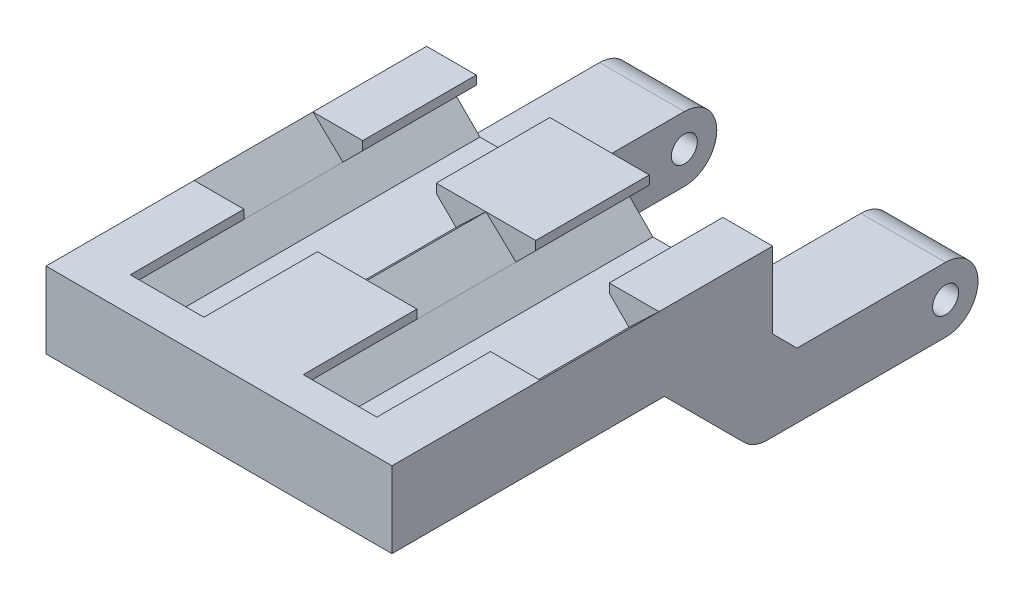
SolidWorks part; units mm, degrees
ref_plane "Front Plane" through (0, 0, 0) normal (0, 0, 1) x (1, 0, 0)
ref_plane "Top Plane" through (0, 0, 0) normal (0, 1, 0) x (1, 0, 0)
ref_plane "Right Plane" through (0, 0, 0) normal (1, 0, 0) x (0, 0, -1)
sketch "Sketch1" plane through (0, 0, 0) normal (0, 0, 1) x (1, 0, 0)
  line L154 (-20, -0.2) -> (-20, -9)
  line L155 (-20, -9) -> (20, -9)
  line L156 (20, -9) -> (20, -0.2)
  line L157 (-6.25, -6) -> (-13.75, -6) construction
  line L171 (14.2535, -0.2) -> (20, -0.2)
  line L172 (14.2535, -1.2207) -> (14.2535, -0.2)
  line L173 (16.5328, -3.5) -> (14.2535, -1.2207)
  line L174 (13.8328, -6.2) -> (16.5328, -3.5)
  line L175 (6.1672, -6.2) -> (13.8328, -6.2)
  line L176 (3.4672, -3.5) -> (6.1672, -6.2)
  line L177 (5.7465, -1.2207) -> (3.4672, -3.5)
  line L178 (5.7465, -0.2) -> (5.7465, -1.2207)
  line L179 (-5.7465, -0.2) -> (5.7465, -0.2)
  line L180 (-5.7465, -1.2207) -> (-5.7465, -0.2)
  line L181 (-3.4672, -3.5) -> (-5.7465, -1.2207)
  line L182 (-6.1672, -6.2) -> (-3.4672, -3.5)
  line L183 (-13.8328, -6.2) -> (-6.1672, -6.2)
  line L184 (-16.5328, -3.5) -> (-13.8328, -6.2)
  line L185 (-14.2535, -1.2207) -> (-16.5328, -3.5)
  line L186 (-14.2535, -0.2) -> (-14.2535, -1.2207)
  line L187 (-20, -0.2) -> (-14.2535, -0.2)
  line L188 (14.2535, -0.2) -> (20, -0.2)
  line L189 (14.2535, -1.2207) -> (14.2535, -0.2)
  line L190 (16.5328, -3.5) -> (14.2535, -1.2207)
  line L191 (13.8328, -6.2) -> (16.5328, -3.5)
  line L192 (6.1672, -6.2) -> (13.8328, -6.2)
  line L193 (3.4672, -3.5) -> (6.1672, -6.2)
  line L194 (5.7465, -1.2207) -> (3.4672, -3.5)
  line L195 (5.7465, -0.2) -> (5.7465, -1.2207)
  line L196 (-5.7465, -0.2) -> (5.7465, -0.2)
  line L197 (-5.7465, -1.2207) -> (-5.7465, -0.2)
  line L198 (-3.4672, -3.5) -> (-5.7465, -1.2207)
  line L199 (-6.1672, -6.2) -> (-3.4672, -3.5)
  line L200 (-13.8328, -6.2) -> (-6.1672, -6.2)
  line L201 (-16.5328, -3.5) -> (-13.8328, -6.2)
  line L202 (-14.2535, -1.2207) -> (-16.5328, -3.5)
  line L203 (-14.2535, -0.2) -> (-14.2535, -1.2207)
  line L204 (-20, -0.2) -> (-14.2535, -0.2)
  dimension "D2" = 3
  dimension "D1" = 0.2
extrude "Boss-Extrude1" add sketch "Sketch1" against normal blind 40 contours L154 L155 L156 L188 L189 L190 L191 L192 L193 L194 L195 L196 L197 L198 L199 L200 L201 L202 L203 L204
sketch "Sketch2" plane through (-20, 0, 0) normal (-1, 0, 0) x (0, 0, 1)
  line L0 (-40, -6.2) -> (0, -6.2) construction
  line L1 (-40, -6.2) -> (0, -6.2)
  line L2 (-20, -0.2) -> (-20, -6.2) construction
  line L3 (-40, -0.2) -> (0, -0.2) construction
  line L5 (-26.8667, -6.2) -> (-13.1333, -6.2)
  line L6 (-26.8667, -6.2) -> (-26.8667, -0.2)
  line L7 (-26.8667, -0.2) -> (-13.1333, -0.2)
  line L8 (-13.1333, -6.2) -> (-13.1333, -0.2)
  line L9 (-26.8667, -6.2) -> (-13.1333, -0.2) construction
  line L10 (-26.8667, -0.2) -> (-13.1333, -6.2) construction
  point P6 (-20, -3.2)
  line M4 (0, -0.2) -> (-40, -0.2)
  dimension "D1" = 13.7333
extrude "Cut-Extrude1" cut sketch "Sketch2" against normal through all contours L1 L8 L6 M4 region at (-20, -3.2, -20)
sketch "Sketch3" plane through (0, 0, 0) normal (0, 0, 1) x (1, 0, 0)
  line L1 (-20, -0.2) -> (20, -0.2)
  line L2 (-20, -0.2) -> (-20, -9)
  line L3 (-20, -9) -> (20, -9)
  line L4 (20, -0.2) -> (20, -9)
extrude "Boss-Extrude2" add sketch "Sketch3" along normal blind 4 contours L2 L3 L4 L1
sketch "Sketch4" plane through (0, 0, -26.8667) normal (0, 0, 1) x (1, 0, 0)
  line L0 (-20, -6.2) -> (-20, -0.2) construction
  line L1 (-13.8328, -6.2) -> (-16.5328, -3.5) construction
  line L2 (-13.8328, -6.2) -> (-20, -6.2) construction
  line L3 (-20, -6.2) -> (-20, -0.2)
  line L4 (-13.8328, -6.2) -> (-16.5328, -3.5)
  line L5 (-13.8328, -6.2) -> (-20, -6.2)
  line L6 (-16.5328, -3.5) -> (-20, -0.2)
  line L7 (6.1672, -6.2) -> (3.4672, -3.5) construction
  line L8 (-3.4672, -3.5) -> (-6.1672, -6.2) construction
  line L9 (6.1672, -6.2) -> (-6.1672, -6.2) construction
  line L10 (6.1672, -6.2) -> (3.4672, -3.5)
  line L11 (-3.4672, -3.5) -> (-6.1672, -6.2)
  line L12 (6.1672, -6.2) -> (-6.1672, -6.2)
  line L13 (-3.4672, -3.5) -> (0, -0.2)
  line L14 (5.7465, -0.2) -> (-5.7465, -0.2) construction
  line L15 (0, -0.2) -> (3.4672, -3.5)
  line L16 (20, -6.2) -> (20, -0.2) construction
  line L17 (20, -6.2) -> (13.8328, -6.2) construction
  line L18 (16.5328, -3.5) -> (13.8328, -6.2) construction
  line L19 (20, -6.2) -> (20, -0.2)
  line L20 (20, -6.2) -> (13.8328, -6.2)
  line L21 (16.5328, -3.5) -> (13.8328, -6.2)
  line L22 (16.5328, -3.5) -> (20, -0.2)
  line L23 (20, -0.2) -> (19.9486, -0.3388)
  line M4 (-20, -0.2) -> (-20, -6.2)
  line M5 (-20, -6.2) -> (-13.8328, -6.2)
  line M6 (-13.8328, -6.2) -> (-16.5328, -3.5)
extrude "Boss-Extrude3" add sketch "Sketch4" along normal up to surface (13.7333 mm away) contours L6 M6 M4 M5 | L15 L13 L11 L12 L10 | L22 L21 L20 L19 region at (-17.9304, -4.1892, -26.8667) region at (0, -4.1892, -26.8667) region at (17.9304, -4.1892, -26.8667) up to face at (0, -2.7802, -13.1333)
sketch "Sketch5" plane through (-20, 0, 0) normal (-1, 0, 0) x (0, 0, 1)
  line L0 (-40, -9) -> (-42.8284, -11.8284)
  line L1 (-60, -15.5784) -> (-39.3817, -15.5784) construction
  line L2 (-60, -11.8284) -> (-39.3817, -11.8284)
  line L3 (-60, -19.3284) -> (-39.3817, -19.3284)
  line L4 (-40, -9) -> (4, -9) construction
  line L5 (-36.7301, -18.2301) -> (-27.5, -9)
  line L6 (-27.5, -9) -> (-40, -9)
  line L7 (-40, -0.2) -> (-40, -9) construction
  arc A0 (-60, -11.8284) -> (-60, -19.3284) centre (-60, -15.5784) ccw
  arc A1 (-39.3817, -19.3284) -> (-39.3817, -11.8284) centre (-39.3817, -15.5784) ccw
  circle A2 centre (-60, -15.5784) radius 1.5
  point P5 (-49.6909, -15.5784)
  line M10 (-40, -9) -> (4, -9)
  dimension "D6" = 3
  dimension "D1" = 7.5
  dimension "D2" = 45
  dimension "D3" = 4
  dimension "D4" = 45
  dimension "D5" = 12.5
  dimension "D7" = 20
extrude "Boss-Extrude4" add sketch "Sketch5" against normal blind 9.8 contours L3 A1 L2 A0 A2 | A1 L5 L0 L2 M10 region at (-20, -11.4295, -34.8962) region at (-20, -15.5784, -49.3108)
mirror "Mirror1" about plane through (0, 0, 0) normal (1, 0, 0) of "Boss-Extrude4"
